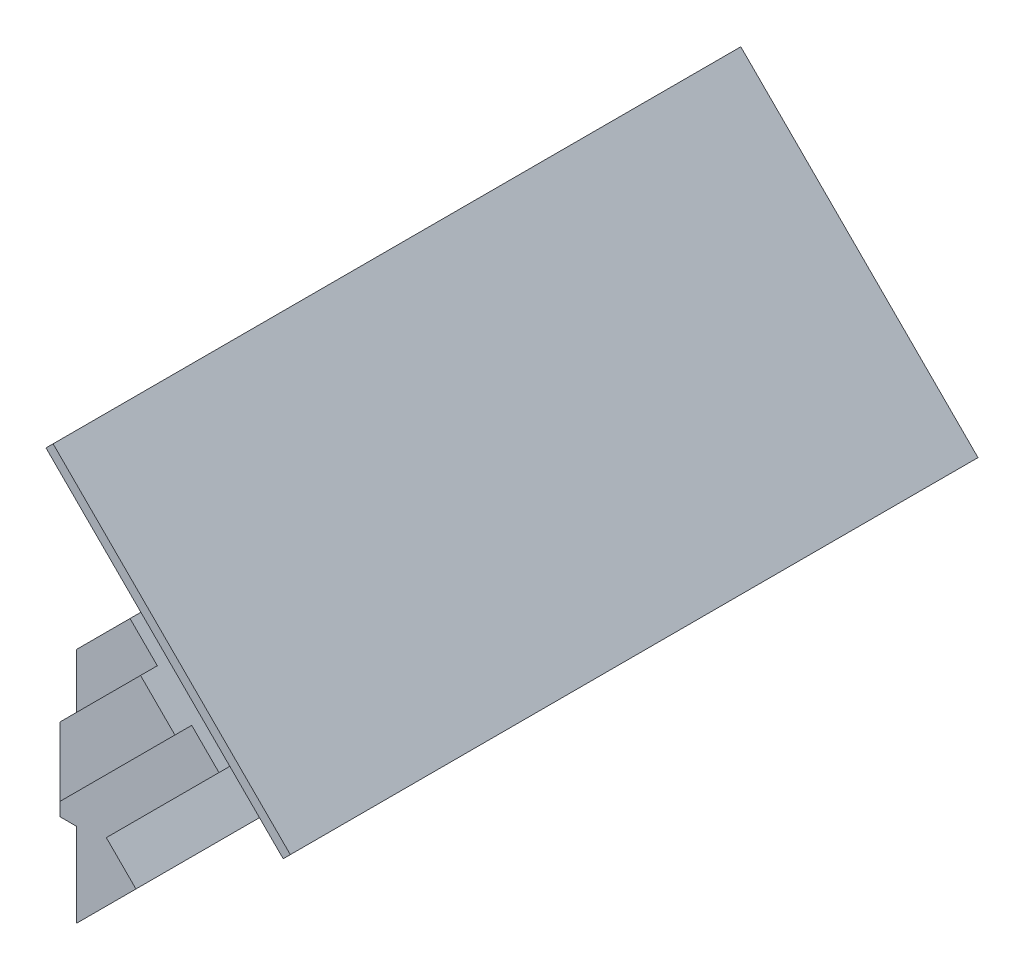
SolidWorks part; units mm, degrees
ref_plane "Front Plane" through (0, 0, 0) normal (0, 0, 1) x (1, 0, 0)
ref_plane "Top Plane" through (0, 0, 0) normal (0, 1, 0) x (1, 0, 0)
ref_plane "Right Plane" through (0, 0, 0) normal (1, 0, 0) x (0, 0, -1)
sketch "Esquisse1" plane through (0, 0, 0) normal (0, 0, 1) x (1, 0, 0)
  line L0 (0, 0) -> (0, 5)
  line L1 (0, 5) -> (-1, 5)
  line L2 (-1, 5) -> (-1, 7.9)
  line L3 (-1, 7.9) -> (0, 7.9)
  line L4 (0, 7.9) -> (0, 14.1421)
  line L5 (0, 14.1421) -> (3.182, 17.3241)
  line L6 (3.182, 17.3241) -> (10.253, 10.253)
  line L7 (10.253, 10.253) -> (0, 0)
  dimension "D1" = 2.9
  dimension "D2" = 45
  dimension "D3" = 10
  dimension "D4" = 5
  dimension "D5" = 1
  dimension "D6" = 14.5
extrude "Main Extrusion" add sketch "Esquisse1" along normal mid plane 30
sketch "Esquisse2" plane through (0, 0, 0) normal (0.7071, -0.7071, 0) x (0, 0, -1)
  line L0 (15, 0) -> (15, 14.5) construction
  line L1 (5, 5) -> (15, 5)
  line L2 (5, 5) -> (5, 14.5)
  line L3 (5, 14.5) -> (15, 14.5)
  line L4 (15, 5) -> (15, 14.5)
  line L5 (-15, 14.5) -> (15, 14.5) construction
  line L6 (-15, 0) -> (15, 0) construction
  dimension "D1" = 5
  dimension "D2" = 10
extrude "Window Extrusion" cut sketch "Esquisse2" against normal blind 2.5
sketch "Esquisse5" plane through (-1.7678, 1.7678, 0) normal (0.7071, -0.7071, 0) x (0, 0, -1)
  line L0 (15, 14.5) -> (5, 14.5) construction
  line L2 (5, 5) -> (15, 5) construction
  circle A0 centre (10, 11.5) radius 1.25
  point P4 (10, 14.5)
  dimension "D1" = 2.5
  dimension "D2" = 6.5
extrude "Window Hole Extrusion" cut sketch "Esquisse5" against normal through all
sketch "Esquisse7" plane through (10.253, 10.253, 0) normal (0.7071, 0.7071, 0) x (0, 0, -1)
  line L0 (-5.1, 2.5) -> (-5.1, 3.55)
  line L1 (-5.1, 3.55) -> (-4.1, 3.55)
  line L2 (-4.1, 3.55) -> (-4.1, 6.45)
  line L3 (-4.1, 6.45) -> (-5.1, 6.45)
  line L4 (-5.1, 6.45) -> (-5.1, 10)
  line L6 (-15, 10) -> (15, 10) construction
  line L7 (-15, 0) -> (-15, 10) construction
  line L18 (-8.1, 10) -> (-5.1, 10)
  line L19 (-8.1, 10) -> (-8.1, 2.5)
  line L20 (-8.1, 2.5) -> (-5.1, 2.5)
  dimension "D1" = 1
  dimension "D2" = 2.9
  dimension "D3" = 3
  dimension "D4" = 6.9
  dimension "D5" = 3.55
  dimension "D6" = 7.5
extrude "Fixation Top MakerBeam Extrusion" add sketch "Esquisse7" along normal blind 10
mirror "Window Symetry" about plane through (0, 0, 0) normal (0, 0, 1) of "Fixation Top MakerBeam Extrusion", "Window Extrusion", "Window Hole Extrusion"
sketch "Esquisse3" plane through (-1, 0, 0) normal (-1, 0, 0) x (0, 0, 1)
  line L0 (15, 7.9) -> (15, 5) construction
  line L1 (0, -55) -> (0, 55) construction
  circle A0 centre (0, 6.45) radius 1.5
  point P5 (15, 6.45)
  dimension "D1" = 3
extrude "Window Hole Fixation" cut sketch "Esquisse3" against normal through all
ref_plane "Plan1" through (3, 0, 0) normal (-1, 0, 0) x (0, 0, 1)
sketch "Esquisse4" plane through (3, 0, 0) normal (-1, 0, 0) x (0, 0, 1)
  circle A0 centre (0, 6.45) radius 4.1
  arc A1 (0.3841, 5) -> (0.3841, 7.9) centre (0, 6.45) ccw construction
  dimension "D1" = 8.2
extrude "Central Fixation" cut sketch "Esquisse4" against normal through all
sketch "Esquisse6" plane through (0, 0, 15) normal (0, 0, 1) x (1, 0, 0)
  line L0 (0, 10.8894) -> (4.8083, 15.6978)
  line L1 (8.4853, 12.0208) -> (3.182, 17.3241) construction
  line L2 (4.8083, 15.6978) -> (6.8589, 13.6472)
  line L3 (6.8589, 13.6472) -> (0, 6.7882)
  line L4 (0, 6.7882) -> (0, 10.8894)
  line L5 (0, 5) -> (0, 0) construction
  point P6 (5.8336, 14.6725)
  point P7 (5.8336, 14.6725)
  dimension "D1" = 2.9
extrude "Boss.-Extru.2" add sketch "Esquisse6" along normal blind 1
sketch "Esquisse8" plane through (17.3241, 17.3241, 0) normal (0.7071, 0.7071, 0) x (0, 0, -1)
  line L0 (-8.1, 10) -> (-1.45, 10)
  line L1 (-1.45, 10) -> (-1.45, 9)
  line L2 (-1.45, 9) -> (1.45, 9)
  line L3 (1.45, 9) -> (1.45, 10)
  line L4 (1.45, 10) -> (8.1, 10)
  line L5 (8.1, 10) -> (8.1, 13)
  line L6 (8.1, 13) -> (-8.1, 13)
  line L7 (-8.1, 13) -> (-8.1, 10)
  line L8 (0, 55) -> (0, -55) construction
  point P9 (0, 9)
  dimension "D1" = 3
  dimension "D2" = 2.9
  dimension "D3" = 1
extrude "Boss.-Extru.6" add sketch "Esquisse8" against normal blind 12
fillet "Congé1" radius 4 2 edges at (0.7071, 16.9706, -8.1) (0.7071, 16.9706, 8.1)
sketch "Esquisse11" plane through (-9.1924, 9.1924, 0) normal (-0.7071, 0.7071, 0) x (0, 0, 1)
  line L0 (-8.1, 24.5) -> (8.1, 24.5) construction
  circle A0 centre (0, 19.5) radius 1.6
  point P4 (0, 24.5)
  dimension "D1" = 3.2
  dimension "D2" = 5
extrude "Enlèv. mat.-Extru.2" cut sketch "Esquisse11" against normal through all
sketch "Esquisse12" plane through (25.3787, 9.2696, 0) normal (-0.7071, -0.7071, 0) x (0, 0, 1)
  line L0 (-8.1, 24.3909) -> (8.1, 24.3909) construction
  line L1 (21, 29.3909) -> (-20, 29.3909)
  line L2 (21, 29.3909) -> (21, 9.3909)
  line L3 (21, 9.3909) -> (-20, 9.3909)
  line L4 (-20, 29.3909) -> (-20, 9.3909)
  line L5 (16, 16.1909) -> (16, 19.0909) construction
  line L6 (-15, 13.8909) -> (-15, 21.3909) construction
  dimension "D1" = 5
  dimension "D2" = 5
  dimension "D3" = 5
  dimension "D4" = 20
extrude "Boss.-Extru.7" add sketch "Esquisse12" along normal blind 0.6
